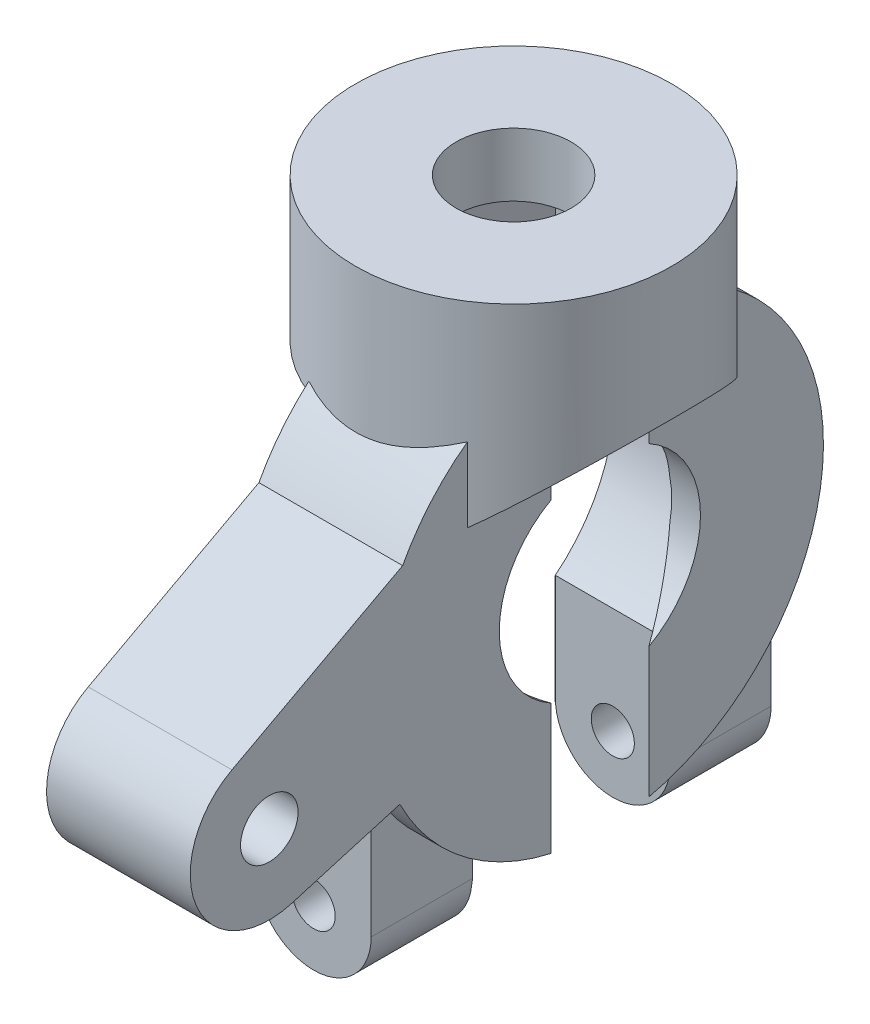
SolidWorks part; units mm, degrees
note: The reader was unsure of these and kept them because the rebuilt part matched: shared geometry of "Sketch3<2>", "Sketch2<2>".
ref_plane "Front Plane" through (0, 0, 0) normal (0, 0, 1) x (1, 0, 0)
ref_plane "Top Plane" through (0, 0, 0) normal (0, 1, 0) x (1, 0, 0)
ref_plane "Right Plane" through (0, 0, 0) normal (1, 0, 0) x (0, 0, -1)
sketch "Sketch1" plane through (0, 0, 0) normal (0, 1, 0) x (1, 0, 0)
  circle A0 centre (0, 0) radius 11
  circle A1 centre (0, 0) radius 4
  dimension "D1" = 22
  dimension "D2" = 8
extrude "Boss-Extrude1" add sketch "Sketch1" along normal blind 10
sketch "Sketch3" plane through (0, 0, 0) normal (1, 0, 0) x (0, 0, -1)
  line L0 (11, 10) -> (-11, 10) construction
  circle A0 centre (0, 21) radius 11
  circle A1 centre (0, 21) radius 15.5563
  dimension "D1" = 22
extrude "Boss-Extrude2" add sketch "Sketch3" along normal mid plane 8
sketch "Sketch2" plane through (0, 10, 0) normal (0, 1, 0) x (1, 0, 0)
  line L0 (-21.6435, 0) -> (19.7802, 0) construction
  line L1 (3.9837, 6.9) -> (-3.9837, 6.9)
  line L2 (-3.9837, 6.9) -> (-7.9674, 0)
  line L3 (-7.9674, 0) -> (-3.9837, -6.9)
  line L4 (-3.9837, -6.9) -> (3.9837, -6.9)
  line L5 (3.9837, -6.9) -> (7.9674, 0)
  line L6 (7.9674, 0) -> (3.9837, 6.9)
  circle A0 centre (0, 0) radius 6.9 construction
  dimension "D1" = 13.8
extrude "Cut-Extrude1" cut sketch "Sketch2" against normal blind 5.6 and the other way through all
sketch "Sketch9" plane through (0, 10, 0) normal (0, 1, 0) x (1, 0, 0)
  line L0 (4, 6.8718) -> (4, 10.247)
  line L1 (4, -6.8718) -> (7.9674, 0)
  line L2 (7.9674, 0) -> (4, 6.8718)
  line L3 (4, -10.247) -> (4, -6.8718)
  arc A0 (4, 10.247) -> (4, -10.247) centre (0, 0) cw
  arc A1 (4, -10.247) -> (4, 10.247) centre (0, 0) ccw construction
  line M1 (4, 10.247) -> (4, 6.8718)
  line M2 (4, 6.8718) -> (7.9674, 0)
  line M3 (7.9674, 0) -> (4, -6.8718)
  line M4 (4, -6.8718) -> (4, -10.247)
  arc M5 (4, -10.247) -> (4, 10.247) centre (0, 0) ccw
extrude "Boss-Extrude4" add sketch "Sketch9" along normal blind 10 contours M5 M1 M2 M3 M4
sketch "Sketch4" plane through (4, 0, 0) normal (1, 0, 0) x (0, 0, -1)
  line L0 (-6.8718, 34.9563) -> (-6.8718, 40.9563)
  line L1 (-6.8718, 40.9563) -> (-13.9144, 40.9563)
  line L2 (-13.9144, 40.9563) -> (-13.9144, 27.9563)
  line L3 (-6.8718, 37.9563) -> (18.7793, 37.9563) construction
  line L4 (-13.9144, 40.9563) -> (18.7793, 40.9563) construction
  line L5 (0, 8.8743) -> (0, 51.341) construction
  line L6 (6.8718, 34.9563) -> (6.8718, 40.9563)
  line L7 (6.8718, 40.9563) -> (13.9144, 40.9563)
  line L8 (13.9144, 40.9563) -> (13.9144, 27.9563)
  arc A0 (-6.8718, 34.9563) -> (-10.247, 9.2953) centre (0, 21) ccw construction
  arc A1 (-13.9144, 27.9563) -> (-6.8718, 34.9563) centre (0, 21) cw
  arc A2 (13.9144, 27.9563) -> (6.8718, 34.9563) centre (0, 21) ccw
  dimension "D1" = 3
  dimension "D2" = 13
extrude "Boss-Extrude3" add sketch "Sketch4" against normal up to surface (8 mm away) up to face at (-4, 17.8591, -9.8289)
extrude "Boss-Extrude5" add sketch "Sketch3<2>" along normal blind 2 from surface at 4 contours A0 | A1 A0 starting at face at (4, 28.6626, 10.5982)
sketch "Sketch3<2>" plane through (0, 0, 0) normal (1, 0, 0) x (0, 0, -1) same geometry as "Sketch3"
extrude "Cut-Extrude2" cut sketch "Sketch2<2>" along normal through all and the other way up to surface (5.6 mm away) other way up to face at (0, 4.4, 4)
sketch "Sketch2<2>" plane through (0, 10, 0) normal (0, 1, 0) x (1, 0, 0) same geometry as "Sketch2"
sketch "Sketch13" plane through (6, 0, 0) normal (1, 0, 0) x (0, 0, -1)
  circle A0 centre (0, 21) radius 7
  dimension "D1" = 14
extrude "Cut-Extrude3" cut sketch "Sketch13" against normal through all both and the other way through all
sketch "Sketch14" plane through (0, 0, 13.9144) normal (0, 0, 1) x (1, 0, 0)
  line L0 (-4, 27.9563) -> (-4, 40.9563) construction
  line L2 (4, 40.9563) -> (4, 27.9563) construction
  line L3 (-4, 40.9563) -> (4, 40.9563) construction
  line L4 (-4, 36.9563) -> (-4, 43.4737)
  line L5 (-4, 43.4737) -> (4, 43.4737)
  line L6 (4, 43.4737) -> (4, 36.9563)
  circle A0 centre (0, 36.9563) radius 1.5
  arc A1 (-4, 36.9563) -> (4, 36.9563) centre (0, 36.9563) cw
  dimension "D1" = 3
  dimension "D2" = 6.5173
extrude "Cut-Extrude5" cut sketch "Sketch14" against normal through all both and the other way through all
sketch "Sketch15" plane through (6, 0, 0) normal (1, 0, 0) x (0, 0, -1)
  circle A0 centre (0, 21) radius 11.7899
extrude "Cut-Extrude6" cut sketch "Sketch15" along normal blind 8 from surface at 0 starting at face at (6, 22.8359, -8.44)
sketch "Sketch16" plane through (-4, 0, 0) normal (-1, 0, 0) x (0, 0, 1)
  line L0 (0, -22.8948) -> (0, 64.8948) construction
  line L1 (23, -23.5851) -> (23, 63.1608) construction
  line L2 (0, 21) -> (82.2467, 34.911) construction
  line L3 (11, 21) -> (-11, 21) construction
  line L4 (25.5993, 20.0432) -> (6.8718, 10)
  line L5 (13.9144, 27.9563) -> (21.4516, 30.1677)
  circle A0 centre (23, 24.8902) radius 2
  arc A1 (6.8718, 12.4106) -> (6.8718, 29.5894) centre (0, 21) ccw construction
  arc A2 (-6.8718, 29.5894) -> (-6.8718, 12.4106) centre (0, 21) ccw construction
  arc A3 (25.5993, 20.0432) -> (21.4516, 30.1677) centre (23, 24.8902) ccw
  arc M14 (10.247, 9.2953) -> (13.9144, 27.9563) centre (0, 21) ccw
  dimension "D2" = 4
  dimension "D3" = 5.5
  dimension "D1" = 80.4
  dimension "19" = 23
extrude "Boss-Extrude6" add sketch "Sketch16" against normal up to surface (10 mm away) contours L4 A3 L5 A0 M14 up to face at (6, 18.5733, 7.4789)
ref_plane "Plane1" through (0, -20, 0) normal (0, -1, 0) x (-1, 0, 0)
mirror "Mirror1" about plane through (0, -20, 0) normal (0, -1, 0) of bodies 112
delete or keep bodies "Body-Delete/Keep 1" type delete bodies bodies 112
